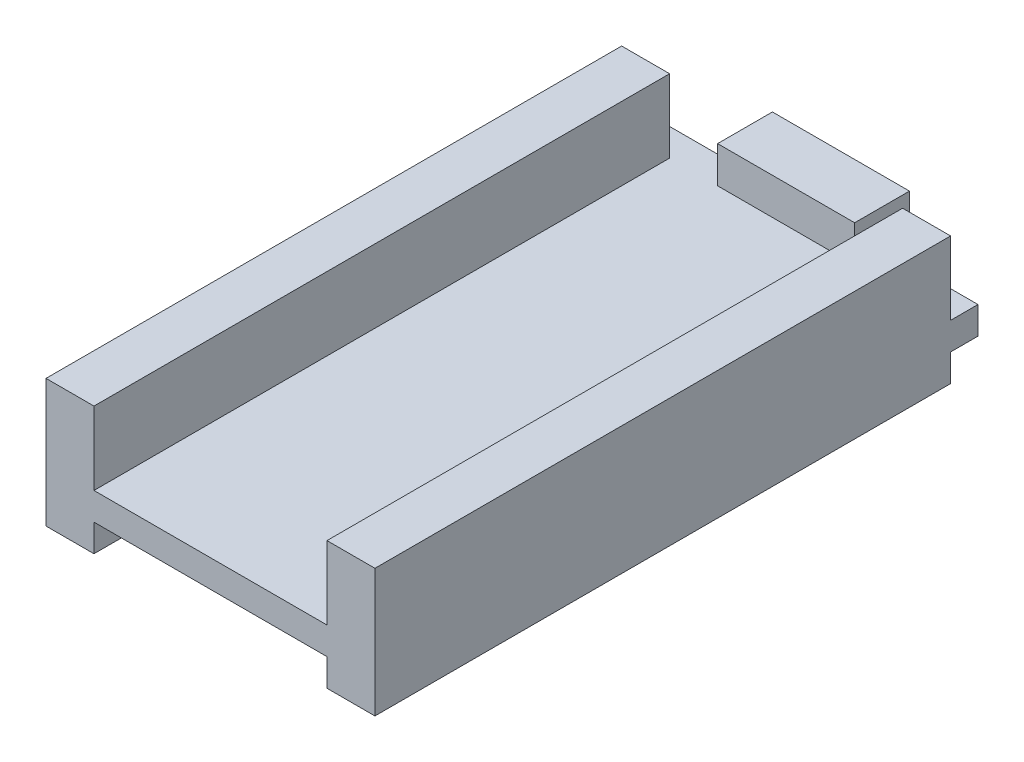
SolidWorks part; units mm, degrees
ref_plane "Front Plane" through (0, 0, 0) normal (0, 0, 1) x (1, 0, 0)
ref_plane "Top Plane" through (0, 0, 0) normal (0, 1, 0) x (1, 0, 0)
ref_plane "Right Plane" through (0, 0, 0) normal (1, 0, 0) x (0, 0, -1)
sketch "Sketch1" plane through (0, 0, 0) normal (0, 1, 0) x (1, 0, 0)
  line L0 (-3.75, 15) -> (-9, 15) construction
  line L1 (-9, -16.5) -> (9, -16.5)
  line L2 (-9, -16.5) -> (-9, 16.5)
  line L3 (-9, 16.5) -> (9, 16.5)
  line L4 (9, -16.5) -> (9, 16.5)
  line L5 (-9, -16.5) -> (9, 16.5) construction
  line L6 (-9, 16.5) -> (9, -16.5) construction
  line L7 (-3.75, 15) -> (3.75, 15)
  line L8 (-3.75, 15) -> (-3.75, 18)
  line L9 (-3.75, 18) -> (3.75, 18)
  line L10 (3.75, 15) -> (3.75, 18)
  line L11 (-3.75, 15) -> (3.75, 18) construction
  line L12 (-3.75, 18) -> (3.75, 15) construction
  line L13 (-9, -16.5) -> (-6.375, -16.5)
  line L14 (-9, -16.5) -> (-9, 15)
  line L15 (-9, 15) -> (-6.375, 15)
  line L16 (-6.375, -16.5) -> (-6.375, 15)
  line L17 (0, 16.5) -> (0, -16.5) construction
  line L18 (9, 15) -> (6.375, 15)
  line L19 (6.375, -16.5) -> (6.375, 15)
  point P0 (0, 0)
  point P6 (0, 16.5)
  dimension "D1" = 18
  dimension "D2" = 33
  dimension "D3" = 1.5
  dimension "D4" = 7.5
extrude "Boss-Extrude1" add sketch "Sketch1" along normal blind 1.5 contours L1 L19 L18 L4 L3 L10 L7 L8 L2 L15 L16 | L1 L16 L15 L2 | L19 L1 L4 L18 | L7 L10 L3 L8 region at (-7.6875, 0, 0.75) region at (0, 0, 0.1274) region at (7.6875, 0, 0.75) region at (0, 0, -15.75)
extrude "Boss-Extrude2" add sketch "Sketch1<3>" along normal blind 2 from surface contours L9 L10 L7 L8 starting at face at (0, 1.5, 0)
sketch "Sketch1<3>" plane through (0, 0, 0) normal (0, 1, 0) x (1, 0, 0) same geometry as "Sketch1"
extrude "Boss-Extrude3" add sketch "Sketch1<4>" along normal blind 4 and the other way blind 3 from surface contours L1 L16 L15 L2 | L19 L1 L4 L18 region at (-7.6875, 0, 0.75) region at (7.6875, 0, 0.75) starting at face at (0, 1.5, -7.875)
sketch "Sketch1<4>" plane through (0, 0, 0) normal (0, 1, 0) x (1, 0, 0) same geometry as "Sketch1"
